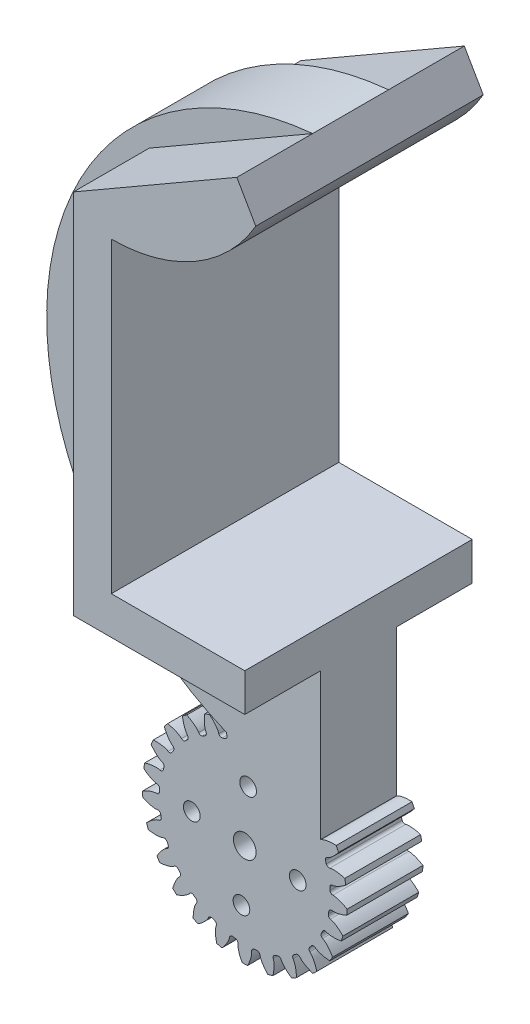
SolidWorks part; units mm, degrees
ref_plane "前视基准面" through (0, 0, 0) normal (0, 0, 1) x (1, 0, 0)
ref_plane "上视基准面" through (0, 0, 0) normal (0, 1, 0) x (1, 0, 0)
ref_plane "右视基准面" through (0, 0, 0) normal (1, 0, 0) x (0, 0, -1)
ref_axis "Axis1" through (0, 0, -88.99) along (0, 0, 1)
sketch "草图1" plane through (0, 0, 0) normal (0, 0, 1) x (1, 0, 0)
  circle A0 centre (0, 0) radius 13.5
extrude "LaShenA" add sketch "草图1" along normal blind 10
sketch "SketchA" plane through (0, 0, 10) normal (0, 0, 1) x (1, 0, 0)
  line L0 (0, 0) -> (0, 13.5) construction
  arc A0 (0.1684, 11.2487) -> (-0.1684, 11.2487) centre (0, 0) ccw
  arc A1 (1.8042, 14.0286) -> (-1.8042, 14.0286) centre (0, 0) ccw
  arc A2 (-0.1684, 11.2487) -> (-0.5533, 11.6043) centre (-0.1741, 11.6287) cw
  arc A3 (0.5533, 11.6043) -> (0.1684, 11.2487) centre (0.1741, 11.6287) cw
  circle A4 centre (0, 0) radius 11.7462 construction
  circle A5 centre (0, 0) radius 13.5 construction
  circle A6 centre (0, 0) radius 11.25 construction
  circle A7 centre (0, 0) radius 12.5 construction
  spline S0 degree 3 poles (0.5533, 11.6043) (0.5561, 11.6473) (0.5611, 11.7224) (0.5725, 11.8116) (0.5848, 11.8743) (0.5957, 11.9239) (0.6097, 11.9808) (0.6273, 12.0449) (0.6489, 12.116) (0.6746, 12.194) (0.7051, 12.2786) (0.7405, 12.3697) (0.7813, 12.4671) (0.8278, 12.5705) (0.8803, 12.6797) (0.9392, 12.7945) (1.0048, 12.9146) (1.0774, 13.0397) (1.1573, 13.1696) (1.2447, 13.3039) (1.3401, 13.4424) (1.4435, 13.5847) (1.5959, 13.7832) (1.7184, 13.9305) (1.8042, 14.0286) knots 0.117691 0.117691 0.117691 0.117691 0.158672 0.189773 0.203463 0.219643 0.238312 0.25947 0.283117 0.309254 0.337879 0.368994 0.402598 0.438691 0.477273 0.518344 0.561905 0.607955 0.656494 0.707522 0.761039 0.817046 0.875541 1 1 1 1
  spline S1 degree 3 poles (-0.5533, 11.6043) (-0.5561, 11.6473) (-0.5611, 11.7224) (-0.5725, 11.8116) (-0.5848, 11.8743) (-0.5957, 11.9239) (-0.6097, 11.9808) (-0.6273, 12.0449) (-0.6489, 12.116) (-0.6746, 12.194) (-0.7051, 12.2786) (-0.7405, 12.3697) (-0.7813, 12.4671) (-0.8278, 12.5705) (-0.8803, 12.6797) (-0.9392, 12.7945) (-1.0048, 12.9146) (-1.0774, 13.0397) (-1.1573, 13.1696) (-1.2447, 13.3039) (-1.3401, 13.4424) (-1.4435, 13.5847) (-1.5959, 13.7832) (-1.7184, 13.9305) (-1.8042, 14.0286) knots 0.117691 0.117691 0.117691 0.117691 0.158672 0.189773 0.203463 0.219643 0.238312 0.25947 0.283117 0.309254 0.337879 0.368994 0.402598 0.438691 0.477273 0.518344 0.561905 0.607955 0.656494 0.707522 0.761039 0.817046 0.875541 1 1 1 1
  dimension "D1" = 0.38
  dimension "Db" = 23.4923
  dimension "Da" = 27
  dimension "Df" = 22.5
  dimension "Dn" = 25
extrude "Cut-ExtrudeA" cut sketch "SketchA" against normal blind 30
pattern_circular "www.KYTool.cn" count 25 over 360 about axis through (0, 0, -88.99) along (0, 0, 1) of "Cut-ExtrudeA"
sketch "草图3" plane through (0, 0, 10) normal (0, 0, 1) x (1, 0, 0)
  line L0 (0, 0) -> (10, 0) construction
  line L1 (10, 0) -> (10, 30)
  line L2 (5, 8.6603) -> (5, 25)
  line L3 (10, 30) -> (-7.6, 30)
  line L4 (-7.6, 30) -> (-7.6, 70.5)
  line L5 (-7.6, 70.5) -> (11.4526, 81.5) construction
  line L6 (5, 25) -> (-12.6, 25)
  line L7 (-12.6, 25) -> (-12.6, 73.3868)
  line L8 (-12.6, 73.3868) -> (8.9526, 85.8301)
  line L9 (8.9526, 85.8301) -> (11.4526, 81.5)
  line L10 (5, 0) -> (5, 8.6603) construction
  line L11 (5, 0) -> (5, 25) construction
  line L12 (-7.6, 70.5) -> (11.9902, 70.5) construction
  arc A0 (10, 0) -> (5, 8.6603) centre (0, 0) ccw
  arc A1 (5, 8.6603) -> (10, 0) centre (0, 0) ccw construction
  arc A2 (-7.6, 70.5) -> (11.4526, 81.5) centre (-7.6, 92.5) ccw
  dimension "D1" = 20
  dimension "D3" = 30
  dimension "D4" = 17.6
  dimension "D5" = 40.5
  dimension "D6" = 22
  dimension "D7" = 120
  dimension "D2" = 5
extrude "凸台-拉伸2" add sketch "草图3" against normal blind 20 and the other way blind 10
sketch "草图4" plane through (0, 0, 20) normal (0, 0, 1) x (1, 0, 0)
  line L0 (10, 0) -> (10, 30) construction
  line L1 (5, 25) -> (5, 8.6603) construction
  line L2 (10, 0) -> (10, 25)
  line L3 (5, 25) -> (5, 8.6603)
  line L4 (5, 25) -> (10, 25)
  arc A0 (10, 0) -> (5, 8.6603) centre (0, 0) ccw construction
  arc A1 (10, 0) -> (5, 8.6603) centre (0, 0) ccw
extrude "切除-拉伸2" cut sketch "草图4" against normal blind 10 contours L2 L4 L3 A1
sketch "草图5" plane through (0, 0, 10) normal (0, 0, 1) x (1, 0, 0)
  line L1 (12.5, -0.6289) -> (12.5, 47.3711) construction
  line L2 (8.9526, 85.8301) -> (-12.6, 73.3868) construction
  line L3 (-12.6, 73.3868) -> (-12.6, 25) construction
  line L4 (-12.6, 25) -> (10, 25) construction
  line L5 (5, 25) -> (5, 12.5399) construction
  line L6 (8.9526, 85.8301) -> (-12.6, 73.3868)
  line L7 (-12.6, 73.3868) -> (-12.6, 25)
  line L8 (-12.6, 25) -> (5, 25)
  line L9 (5, 25) -> (5, 9.4839)
  arc A0 (8.9526, 85.8301) -> (5, 9.4839) centre (12.5, 47.3711) ccw
  arc A1 (5, 9.4839) -> (12.5, 8.7487) centre (12.5, 47.3711) ccw construction
  point P0 (0, 0)
  dimension "D2" = 48
extrude "凸台-拉伸3" add sketch "草图5" against normal blind 10 contours A0 L9 L8 L7 L6 region at (-13.0456, 42.4923, 10)
sketch "草图6" plane through (0, 0, -10) normal (0, 0, -1) x (-1, 0, 0)
  line L0 (-5, 25) -> (-5, 8.6603) construction
  line L1 (-10, 0) -> (-10, 30) construction
  line L2 (-5, 25) -> (-5, 8.6603)
  line L3 (-10, 0) -> (-10, 25)
  line L4 (-5, 25) -> (-10, 25)
  arc A1 (-5, 8.6603) -> (-10, 0) centre (9.2705, -5.3523) ccw
extrude "切除-拉伸3" cut sketch "草图6" against normal blind 10
sketch "草图7" plane through (0, 0, 10) normal (0, 0, 1) x (1, 0, 0)
  line L0 (-8.084, 0.5086) -> (-5.8884, 0.3705) construction
  line L1 (-13.4734, 0.8477) -> (-8.084, 0.5086) construction
  line L2 (1.497, -0.0942) -> (5.8884, -0.3705) construction
  line L3 (-5.8884, 0.3705) -> (-1.497, 0.0942) construction
  line L4 (-1.497, 0.0942) -> (1.497, -0.0942) construction
  line L5 (8.084, -0.5086) -> (13.4734, -0.8477) construction
  line L6 (5.8884, -0.3705) -> (8.084, -0.5086) construction
  arc A0 (13.446, -1.206) -> (13.4911, -0.4888) centre (0, 0) ccw construction
  circle A3 centre (0, 0) radius 1.5
  circle A6 centre (-6.9862, 0.4395) radius 1.1
  circle A7 centre (0.4395, 6.9862) radius 1.1
  circle A8 centre (6.9862, -0.4395) radius 1.1
  circle A9 centre (-0.4395, -6.9862) radius 1.1
  point P7 (0, 0)
  point P20 (0, 0)
  point P21 (0, 0)
  dimension "D1" = 2.2
  dimension "D2" = 7
  dimension "D5" = 3
  dimension "D3" = 4
extrude "切除-拉伸4" cut sketch "草图7" against normal through all
sketch "草图8" plane through (0, 0, 10) normal (0, 0, 1) x (1, 0, 0)
  line L0 (10, 8.842) -> (10, 7.1893)
  arc A0 (10.6273, 8.3253) -> (10.1692, 8.879) centre (0, 0) ccw construction
  arc A1 (10.1692, 8.879) -> (10, 8.842) centre (11.4744, 2.5136) ccw construction
  arc A2 (10.6273, 8.3253) -> (10.1692, 8.879) centre (0, 0) ccw
  arc A3 (10.1692, 8.879) -> (10, 8.842) centre (11.4744, 2.5136) ccw
  spline S0 degree 3 poles (1738.4264, -2443.8996) (-104.1963, 113.4638) (20.9319, 30.8942) (10.4994, 8.0337) (10.4325, 7.8967) (10.3657, 7.7684) (10.2995, 7.6486) (10.2341, 7.5374) (10.1701, 7.4345) (10.1076, 7.3399) (2.0553, -4.2166) (-66.9639, 27.9319) (-1831.3353, 2374.8524) knots -23.488005 -23.488005 -23.488005 -23.488005 0.41017 0.461198 0.509737 0.555786 0.599347 0.640418 0.679001 0.715094 0.748698 14.130347 14.130347 14.130347 14.130347 only from (10.6273, 8.3253) to (10, 7.1893) construction
  spline S1 degree 3 poles (10.6273, 8.3253) (10.5865, 8.2264) (10.5229, 8.0819) (10.4325, 7.8967) (10.3657, 7.7684) (10.2995, 7.6486) (10.2341, 7.5374) (10.1701, 7.4345) (10.1076, 7.3399) (10.0513, 7.2589) (10.0154, 7.2099) (10, 7.1893) knots 0.358993 0.358993 0.358993 0.358993 0.461198 0.509737 0.555786 0.599347 0.640418 0.679001 0.715094 0.748698 0.773183 0.773183 0.773183 0.773183
  point P9 (0, 0)
  point P10 (0, 0)
extrude "切除-拉伸5" cut sketch "草图8" against normal blind 10
